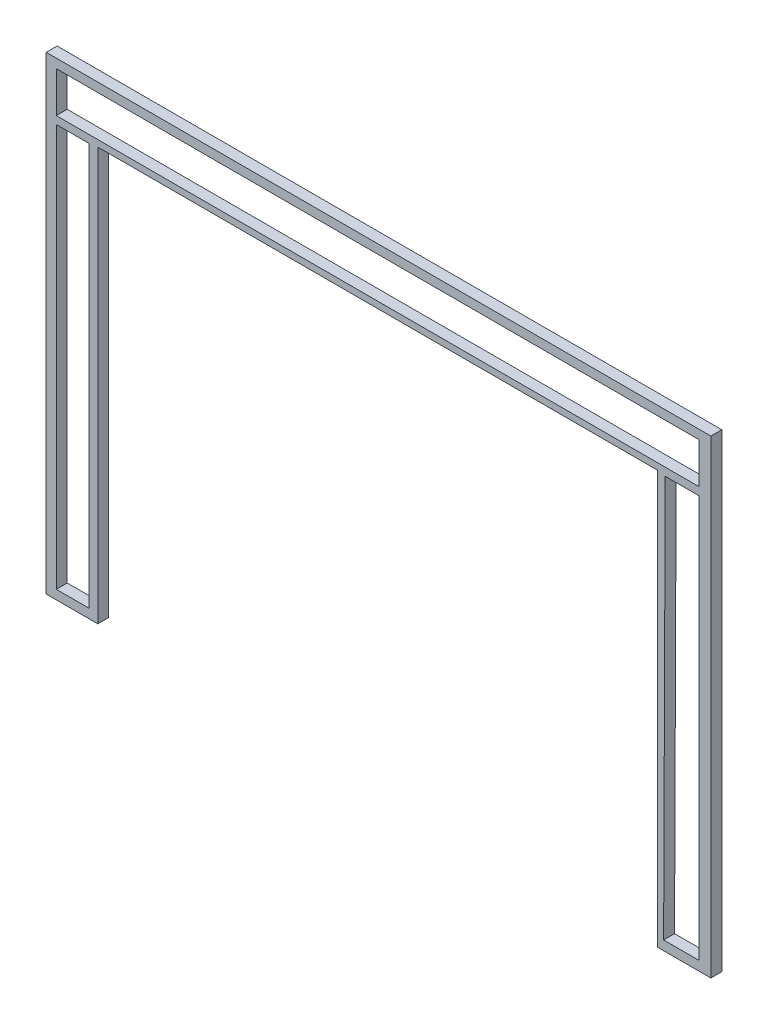
SolidWorks part; units mm, degrees
ref_plane "Alzado" through (0, 0, 0) normal (0, 0, 1) x (1, 0, 0)
ref_plane "Planta" through (0, 0, 0) normal (0, 1, 0) x (1, 0, 0)
ref_plane "Vista lateral" through (0, 0, 0) normal (1, 0, 0) x (0, 0, -1)
sketch "Croquis1" plane through (0, 0, 0) normal (0, 0, 1) x (1, 0, 0)
  line L1 (-349.1298, 1148.1965) -> (-301.9, 1148.1965)
  line L2 (-339.9213, 1156.5681) -> (-339.9213, 1524.98)
  line L3 (-339.9213, 1524.98) -> (-309.8589, 1524.98)
  line L4 (-309.8589, 1524.98) -> (-309.8589, 1156.5681)
  line L6 (-301.9, 1148.1965) -> (-301.9, 1526.1196)
  line L7 (-301.9, 1526.1196) -> (210.142, 1526.1196)
  line L8 (210.142, 1526.1196) -> (210.142, 1148.0282)
  line L11 (215.9591, 1156.5681) -> (217.4078, 1524.8341)
  line L12 (217.4078, 1524.8341) -> (248.3749, 1524.8341)
  line L13 (248.3749, 1524.8341) -> (248.3749, 1156.5681)
  line L14 (210.142, 1148.0282) -> (259.1931, 1148.0282)
  line L16 (19.7067, 1532.0598) -> (-339.9213, 1532.0598)
  line L18 (-339.9213, 1156.5681) -> (-309.8589, 1156.5681)
  line L20 (215.9591, 1156.5681) -> (248.3749, 1156.5681)
  line L21 (-349.1298, 1148.1965) -> (-349.1298, 1577.6064)
  line L22 (-349.1298, 1577.6064) -> (259.1931, 1577.6064)
  line L23 (259.1931, 1577.6064) -> (259.1931, 1148.0282)
  line L24 (19.7067, 1569.2942) -> (-339.9213, 1569.2942)
  line L25 (-339.9213, 1569.2942) -> (-339.9213, 1532.0598)
  line L27 (19.7067, 1569.2942) -> (248.3749, 1569.2942)
  line L28 (248.3749, 1569.2942) -> (248.3749, 1532.0598)
  line L29 (248.3749, 1532.0598) -> (19.7067, 1532.0598)
  point P21 (0, 0)
extrude "Saliente-Extruir1" add sketch "Croquis1" along normal blind 10
